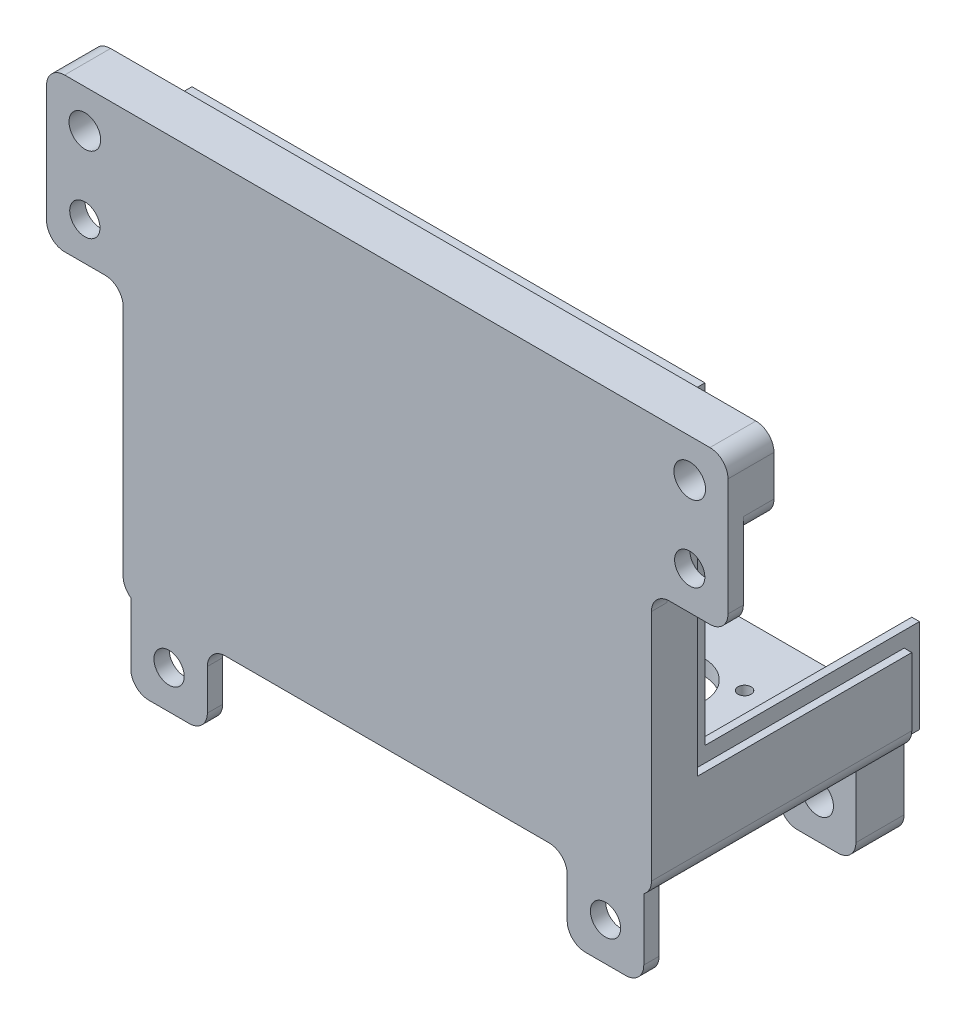
SolidWorks part; units mm, degrees
material "ABS"
ref_plane "X-Y Datum" through (0, 0, 0) normal (0, 0, 1) x (1, 0, 0)
ref_plane "X-Z Datum" through (0, 0, 0) normal (0, 1, 0) x (1, 0, 0)
ref_plane "Y-Z Datum" through (0, 0, 0) normal (1, 0, 0) x (0, 0, -1)
sketch "Sketch1" plane through (0, 0, 0) normal (0, 0, 1) x (1, 0, 0)
  line L0 (6.33, 73.27) -> (88.87, 73.27)
  line L1 (7.6, 72) -> (87.6, 72) construction
  line L2 (7.6, 72) -> (7.6, 9.5) construction
  line L3 (7.6, 9.5) -> (87.6, 9.5) construction
  line L4 (87.6, 72) -> (87.6, 9.5) construction
  line L5 (88.87, 73.27) -> (88.87, 8.23)
  line L6 (6.33, 8.23) -> (88.87, 8.23)
  line L7 (6.33, 73.27) -> (6.33, 8.23)
  circle A0 centre (12.6, 67) radius 2.125 construction
  circle A1 centre (82.6, 67) radius 2.125 construction
  circle A2 centre (82.6, 17) radius 2.125 construction
  circle A3 centre (12.6, 17) radius 2.125 construction
  dimension "D1" = 1.27
extrude "Boss-Extrude1" add sketch "Sketch1" along normal blind 43.18
shell "Shell1" thickness 2.54 removed face at (47.6, 40.75, 0) removed face at (47.6, 73.27, 21.59) outward yes
sketch "Sketch2" plane through (97.1, 5.69, 0) normal (0, 1, 0) x (0, 0, -1)
  line L0 (-9.166, 49.5) -> (-32.766, 49.5) construction
  line L1 (-32.766, 71.1371) -> (-32.766, 27.8629) construction
  line L2 (-32.766, 71.1371) -> (-9.166, 71.1371) construction
  line L3 (-9.166, 71.1371) -> (-9.166, 54.9902) construction
  line L4 (-32.766, 27.8629) -> (-9.166, 27.8629) construction
  line L5 (-32.766, 71.1371) -> (-9.166, 27.8629) construction
  line L6 (-9.166, 71.1371) -> (-32.766, 27.8629) construction
  line L8 (-9.166, 54.9902) -> (-7.166, 54.9902) construction
  line L9 (-7.166, 54.9902) -> (-7.166, 44.0098) construction
  line L10 (-9.166, 44.0098) -> (-7.166, 44.0098) construction
  line L11 (-9.166, 49.5) -> (-7.166, 44.0098) construction
  line L12 (-7.166, 54.9902) -> (-9.166, 49.5) construction
  line L13 (-43.18, 49.5) -> (-33.02, 49.5) construction
  line L14 (-43.18, 90.77) -> (-43.18, 8.23) construction
  line L16 (-9.166, 44.0098) -> (-9.166, 27.8629) construction
  line L17 (-33.02, 71.3911) -> (-8.912, 71.3911)
  line L18 (-8.912, 71.3911) -> (-8.912, 55.2442)
  line L19 (-8.912, 55.2442) -> (-6.912, 55.2442)
  line L20 (-6.912, 55.2442) -> (-6.912, 43.7558)
  line L21 (-8.912, 43.7558) -> (-6.912, 43.7558)
  line L22 (-8.912, 43.7558) -> (-8.912, 27.6089)
  line L23 (-33.02, 27.6089) -> (-8.912, 27.6089)
  line L24 (-33.02, 71.3911) -> (-33.02, 27.6089)
  circle A0 centre (-10.166, 73.2) radius 1.085
  circle A1 centre (-10.166, 25.8) radius 1.085
  circle A2 centre (-28.266, 24.3) radius 1.085
  circle A3 centre (-28.266, 74.7) radius 1.085
  point P10 (-20.966, 49.5)
  point P25 (-20.966, 49.5)
  point P34 (-20.966, 49.5)
  dimension "D1" = 0.254
extrude "Cut-Extrude1" cut sketch "Sketch2" along normal through all
fillet "Fillet1" radius 6.2001 4 edges at (25.7089, 6.96, 33.02) (69.4911, 6.96, 33.02) (69.4911, 6.96, 8.912) (25.7089, 6.96, 8.912)
fillet "Fillet2" radius 1 4 edges at (53.3442, 6.96, 8.912) (53.3442, 6.96, 6.912) (41.8558, 6.96, 8.912) (41.8558, 6.96, 6.912)
sketch "Sketch6" plane through (3.79, 0, 0) normal (-1, 0, 0) x (0, 0, 1)
  line L5 (0, 73.27) -> (35.56, 73.27)
  line L6 (0, 73.27) -> (0, 22.47)
  line L7 (0, 22.47) -> (35.56, 22.47)
  line L8 (35.56, 73.27) -> (35.56, 22.47)
extrude "Cut-Extrude2" cut sketch "Sketch6" against normal through all
sketch "Sketch3" plane through (0, 0, 43.18) normal (0, 0, -1) x (-1, 0, 0)
  line L0 (-86.5144, 72) -> (-78.6856, 72)
  line L1 (-7.6, 70.9144) -> (-7.6, 63.0856)
  line L3 (-86.5144, 72) -> (-78.6856, 72) construction
  line L4 (-87.6, 70.9144) -> (-87.6, 63.0856) construction
  line L5 (-87.6, 9.5) -> (-7.6, 9.5) construction
  line L6 (-7.6, 70.9144) -> (-7.6, 63.0856) construction
  line L7 (-8.6856, 72) -> (-16.5144, 72)
  line L8 (-7.6, 20.9144) -> (-7.6, 13.0856)
  line L9 (-87.6, 20.9144) -> (-87.6, 13.0856)
  line L10 (-87.6, 20.9144) -> (-87.6, 13.0856) construction
  line L11 (-16.5144, 72) -> (-8.6856, 72) construction
  line L12 (-7.6, 20.9144) -> (-7.6, 13.0856) construction
  line L13 (-87.6, 70.9144) -> (-87.6, 63.0856)
  circle A0 centre (-82.6, 67) radius 2.125
  circle A1 centre (-12.6, 67) radius 2.125
  circle A2 centre (-12.6, 17) radius 2.125
  circle A3 centre (-82.6, 17) radius 2.125
  arc A4 (-87.6, 63.0856) -> (-78.6856, 72) centre (-82.6, 67) ccw
  arc A5 (-16.5144, 72) -> (-7.6, 63.0856) centre (-12.6, 67) ccw
  arc A6 (-87.6, 13.0856) -> (-87.6, 20.9144) centre (-82.6, 17) ccw
  arc A7 (-7.6, 20.9144) -> (-7.6, 13.0856) centre (-12.6, 17) ccw
  arc A8 (-86.5144, 72) -> (-87.6, 70.9144) centre (-82.6, 67) ccw
  arc A9 (-7.6, 70.9144) -> (-8.6856, 72) centre (-12.6, 67) ccw
  point P18 (-47.6, 40.75)
extrude "Boss-Extrude2" add sketch "Sketch3" along normal blind 9.3904
sketch "Sketch7" plane through (0, 0, 0) normal (0, 0, -1) x (-1, 0, 0)
  line L0 (-91.41, 22.47) -> (-90.14, 22.47)
  line L1 (-91.41, 22.47) -> (-88.87, 22.47) construction
  line L2 (-88.87, 8.23) -> (-88.87, 5.69) construction
  line L3 (-3.79, 5.69) -> (-91.41, 5.69) construction
  line L4 (-90.14, 22.47) -> (-90.14, 6.96)
  line L5 (-90.14, 6.96) -> (-5.06, 6.96)
  line L6 (-5.06, 6.96) -> (-5.06, 22.47)
  line L7 (-6.33, 22.47) -> (-3.79, 22.47) construction
  line L8 (-5.06, 22.47) -> (-3.79, 22.47)
  line L9 (-3.79, 22.47) -> (-3.79, 5.69)
  line L10 (-3.79, 5.69) -> (-91.41, 5.69)
  line L11 (-91.41, 5.69) -> (-91.41, 22.47)
extrude "Cut-Extrude3" cut sketch "Sketch7" against normal blind 2.54
sketch "Sketch8" plane through (0, 22.47, 0) normal (0, 1, 0) x (1, 0, 0)
  line L0 (5.06, -2.54) -> (5.06, -35.56)
  line L1 (6.33, -35.56) -> (3.79, -35.56) construction
  line L2 (5.06, -35.56) -> (3.79, -35.56)
  line L3 (3.79, -35.56) -> (3.79, -2.54)
  line L4 (3.79, -2.54) -> (5.06, -2.54)
  line L5 (90.14, -2.54) -> (90.14, -35.56)
  line L6 (91.41, -35.56) -> (88.87, -35.56) construction
  line L7 (90.14, -35.56) -> (91.41, -35.56)
  line L8 (91.41, -35.56) -> (91.41, -2.54)
  line L9 (91.41, -2.54) -> (90.14, -2.54)
extrude "Cut-Extrude4" cut sketch "Sketch8" against normal blind 2.54
sketch "Sketch10" plane through (0, 73.27, 0) normal (0, 1, 0) x (1, 0, 0)
  line L0 (3.79, -2.54) -> (3.79, -35.56) construction
  line L1 (3.79, -35.5747) -> (91.41, -35.5747)
  line L2 (3.79, -35.5747) -> (3.79, -45.72)
  line L3 (3.79, -45.72) -> (91.41, -45.72)
  line L4 (91.41, -35.5747) -> (91.41, -45.72)
extrude "Boss-Extrude3" add sketch "Sketch10" along normal blind 2.54
sketch "Sketch9" plane through (0, 0, 35.56) normal (0, 0, -1) x (-1, 0, 0)
  line L0 (-90.14, 73.27) -> (-90.14, 74.54)
  line L1 (-90.14, 19.93) -> (-91.41, 19.93)
  line L2 (-90.14, 19.93) -> (-90.14, 73.27)
  line L4 (-91.41, 19.93) -> (-91.41, 73.27)
  line L5 (-5.06, 19.93) -> (-3.79, 19.93)
  line L6 (-5.06, 19.93) -> (-5.06, 73.27)
  line L8 (-3.79, 19.93) -> (-3.79, 73.27)
  line L9 (-90.14, 74.54) -> (-5.06, 74.54)
  line L10 (-5.06, 74.54) -> (-5.06, 73.27)
  line L11 (-3.79, 73.27) -> (-3.79, 75.81)
  line L12 (-3.79, 75.81) -> (-91.41, 75.81)
  line L13 (-91.41, 75.81) -> (-91.41, 73.27)
extrude "Cut-Extrude5" cut sketch "Sketch9" against normal blind 2.54
sketch "Sketch11" plane through (0, 5.69, 0) normal (0, -1, 0) x (1, 0, 0)
  line L0 (47.6, 45.72) -> (47.6, -4.8901) construction
  line L5 (3.79, 45.72) -> (91.41, 45.72) construction
  line L6 (90.14, 10.54) -> (77.44, 10.54)
  line L7 (77.44, 2.54) -> (77.44, 10.54)
  line L8 (90.14, 2.54) -> (77.44, 2.54)
  line L9 (90.14, 2.54) -> (90.14, 10.54)
  line L10 (5.06, 2.54) -> (5.06, 10.54)
  line L11 (5.06, 2.54) -> (17.76, 2.54)
  line L12 (17.76, 2.54) -> (17.76, 10.54)
  line L13 (5.06, 10.54) -> (17.76, 10.54)
extrude "Boss-Extrude4" add sketch "Sketch11" along normal blind 12.7
sketch "Sketch12" plane through (0, 0, 2.54) normal (0, 0, -1) x (-1, 0, 0)
  line L0 (-90.14, 5.69) -> (-77.44, 5.69) construction
  line L1 (-83.79, 5.69) -> (-83.79, -7.01) construction
  line L2 (-77.44, -7.01) -> (-90.14, -7.01) construction
  line L3 (-17.76, 5.69) -> (-5.06, 5.69) construction
  line L4 (-11.41, 5.69) -> (-11.41, -7.01) construction
  line L5 (-5.06, -7.01) -> (-17.76, -7.01) construction
  circle A0 centre (-83.79, -0.66) radius 2.625
  circle A1 centre (-11.41, -0.66) radius 2.625
  point P16 (-83.79, -0.66)
  point P17 (-11.41, -0.66)
extrude "Cut-Extrude6" cut sketch "Sketch12" against normal through all
sketch "Sketch13" plane through (3.79, 0, 0) normal (-1, 0, 0) x (0, 0, 1)
  line L0 (45.72, 75.81) -> (45.72, 5.69) construction
  line L1 (38.1, 75.81) -> (45.72, 75.81)
  line L2 (38.1, 75.81) -> (38.1, 63.11)
  line L3 (38.1, 63.11) -> (45.72, 63.11)
  line L4 (45.72, 75.81) -> (45.72, 63.11)
extrude "Boss-Extrude5" add sketch "Sketch13" along normal blind 12.7
sketch "Sketch14" plane through (0, 0, 38.1) normal (0, 0, -1) x (-1, 0, 0)
  line L0 (2.56, 63.11) -> (2.56, 75.81) construction
  line L1 (8.91, 63.11) -> (-3.79, 63.11) construction
  line L2 (8.91, 75.81) -> (-91.41, 75.81) construction
  circle A0 centre (2.56, 69.46) radius 2.625
extrude "Cut-Extrude7" cut sketch "Sketch14" against normal through all
ref_plane "Plane1" through (47.6, 0, 0) normal (-1, 0, 0) x (0, 0, 1)
mirror "Mirror1" about plane through (47.6, 0, 0) normal (-1, 0, 0) of "Boss-Extrude5", "Cut-Extrude7"
sketch "Sketch15" plane through (0, 0, 45.72) normal (0, 0, 1) x (1, 0, 0)
  line L1 (5.06, 5.69) -> (17.76, 5.69)
  line L2 (5.06, 5.69) -> (5.06, -7.01)
  line L3 (5.06, -7.01) -> (17.76, -7.01)
  line L4 (17.76, 5.69) -> (17.76, -7.01)
  line L5 (77.44, 5.69) -> (90.14, 5.69)
  line L6 (77.44, 5.69) -> (77.44, -7.01)
  line L7 (77.44, -7.01) -> (90.14, -7.01)
  line L8 (90.14, 5.69) -> (90.14, -7.01)
  line L9 (3.79, 63.11) -> (-8.91, 63.11)
  line L10 (3.79, 63.11) -> (3.79, 50.41)
  line L11 (3.79, 50.41) -> (-8.91, 50.41)
  line L12 (-8.91, 63.11) -> (-8.91, 50.41)
  line L13 (91.41, 63.11) -> (104.11, 63.11)
  line L14 (91.41, 63.11) -> (91.41, 50.41)
  line L15 (91.41, 50.41) -> (104.11, 50.41)
  line L16 (104.11, 63.11) -> (104.11, 50.41)
  circle A0 centre (11.41, -0.66) radius 2.508
  circle A1 centre (83.79, -0.66) radius 2.508
  circle A2 centre (-2.56, 56.76) radius 2.508
  circle A3 centre (97.76, 56.76) radius 2.508
extrude "Boss-Extrude6" add sketch "Sketch15" against normal blind 2.54
fillet "Fillet3" radius 3 28 edges at (6.33, 73.27, 39.3774) (88.87, 73.27, 39.3774) (88.87, 8.23, 21.59) (6.33, 8.23, 21.59) (-8.91, 75.81, 41.91) (3.79, 63.11, 40.64) (-8.91, 63.11, 40.64) (-8.91, 50.41, 44.45) (3.79, 50.41, 44.45) (17.76, -7.01, 6.54) (17.76, 5.69, 6.54) (5.06, -7.01, 6.54) (77.44, -7.01, 6.54) (77.44, 5.69, 6.54) (90.14, -7.01, 6.54) (17.76, 5.69, 44.45) (17.76, -7.01, 44.45) (5.06, -7.01, 44.45) (3.79, 5.69, 24.13) (77.44, 5.69, 44.45) (77.44, -7.01, 44.45) (90.14, -7.01, 44.45) (91.41, 5.69, 24.13) (91.41, 63.11, 40.64) (104.11, 63.11, 40.64) (91.41, 50.41, 44.45) (104.11, 50.41, 44.45) (104.11, 75.81, 41.91)
